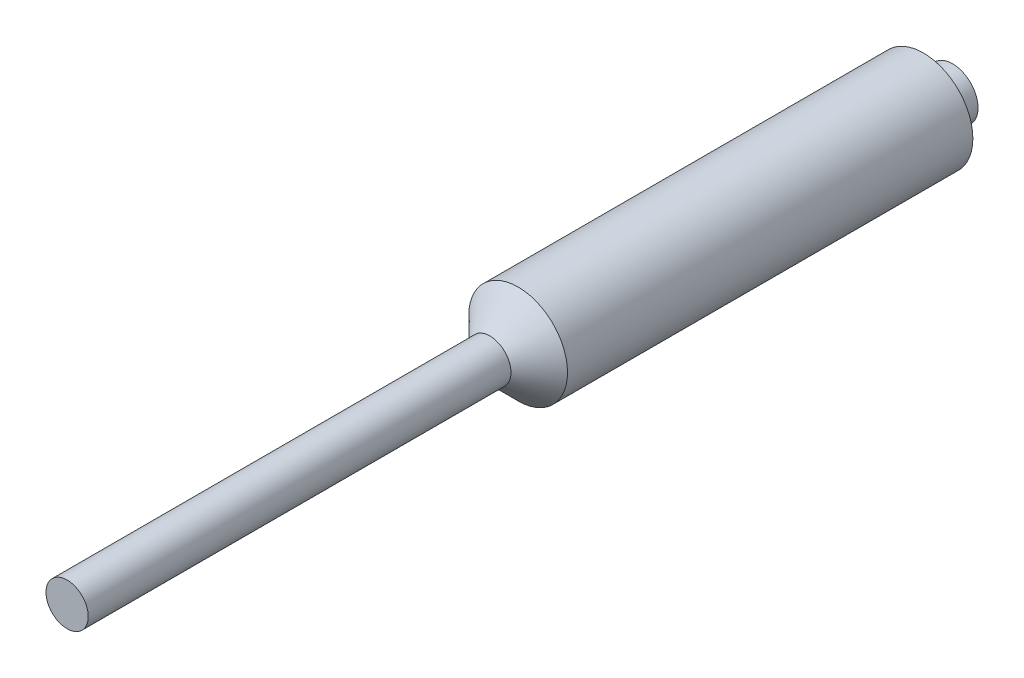
SolidWorks part; units mm, degrees
material "Alloy Steel (SS)"
ref_plane "Front" through (0, 0, 0) normal (0, 0, 1) x (1, 0, 0)
ref_plane "Top" through (0, 0, 0) normal (0, 1, 0) x (1, 0, 0)
ref_plane "Right" through (0, 0, 0) normal (1, 0, 0) x (0, 0, -1)
sketch "Sketch1" plane through (0, 0, 0) normal (0, 0, 1) x (1, 0, 0)
  circle A0 centre (0, 0) radius 5.4927
  dimension "D1" = 10.9855
extrude "Boss-Extrude1" add sketch "Sketch1" along normal blind 49.53
sketch "Sketch2" plane through (0, 0, 49.53) normal (0, 0, 1) x (1, 0, 0)
  circle A0 centre (0, 0) radius 2.3495
  dimension "D1" = 4.699
extrude "Boss-Extrude2" add sketch "Sketch2" along normal blind 45.72
chamfer "Chamfer1" distance 4.445 angle 45 1 edges at (5.4927, 0, 49.53)
sketch "Sketch3" plane through (0, 0, 0) normal (0, 0, -1) x (-1, 0, 0)
  circle A0 centre (0, 0) radius 2.8321
  dimension "D1" = 5.6642
extrude "Boss-Extrude3" add sketch "Sketch3" along normal blind 3.2385
